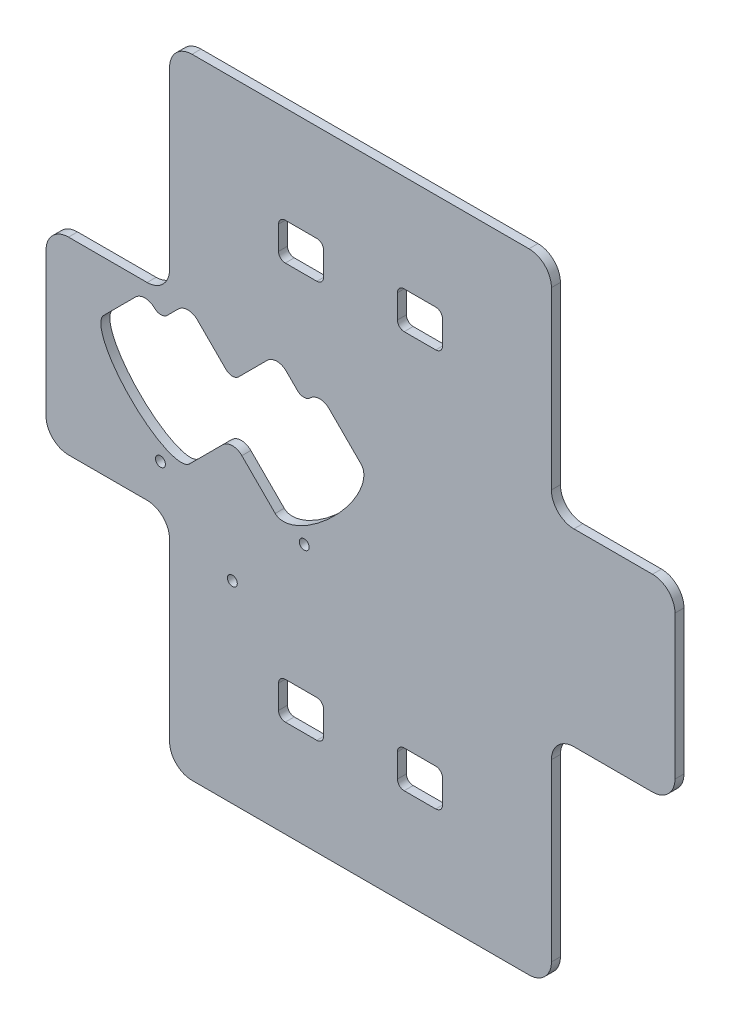
SolidWorks part; units mm, degrees
ref_plane "前视基准面" through (0, 0, 0) normal (0, 0, 1) x (1, 0, 0)
ref_plane "上视基准面" through (0, 0, 0) normal (0, 1, 0) x (1, 0, 0)
ref_plane "右视基准面" through (0, 0, 0) normal (1, 0, 0) x (0, 0, -1)
other "Configuration Table"
sketch "草图1" plane through (0, 0, 0) normal (0, 0, 1) x (1, 0, 0)
  line L24 (85, 52) -> (85, 130)
  line L25 (75, 140) -> (-75, 140)
  line L26 (-85, 130) -> (-85, 52)
  line L27 (-95, 42) -> (-130, 42)
  line L28 (-140, 32) -> (-140, -32)
  line L29 (-130, -42) -> (-95, -42)
  line L30 (-85, -52) -> (-85, -130)
  line L31 (-75, -140) -> (75, -140)
  line L32 (85, -130) -> (85, -52)
  line L33 (95, -42) -> (130, -42)
  line L34 (140, -32) -> (140, 32)
  line L35 (130, 42) -> (95, 42)
  arc A24 (85, 130) -> (75, 140) centre (75, 130) ccw
  arc A25 (-75, 140) -> (-85, 130) centre (-75, 130) ccw
  arc A26 (-95, 42) -> (-85, 52) centre (-95, 52) ccw
  arc A27 (-130, 42) -> (-140, 32) centre (-130, 32) ccw
  arc A28 (-140, -32) -> (-130, -42) centre (-130, -32) ccw
  arc A29 (-85, -52) -> (-95, -42) centre (-95, -52) ccw
  arc A30 (-85, -130) -> (-75, -140) centre (-75, -130) ccw
  arc A31 (75, -140) -> (85, -130) centre (75, -130) ccw
  arc A32 (95, -42) -> (85, -52) centre (95, -52) ccw
  arc A33 (130, -42) -> (140, -32) centre (130, -32) ccw
  arc A34 (140, 32) -> (130, 42) centre (130, 32) ccw
  arc A35 (85, 52) -> (95, 42) centre (95, 52) ccw
extrude "凸台-拉伸1" add sketch "草图1" along normal blind 4
sketch "草图2" plane through (0, 0, 4) normal (0, 0, 1) x (1, 0, 0)
  line L0 (30, -96.75) -> (36.5, -96.75) construction
  line L1 (33.5, -96.75) -> (19.4366, -96.75)
  line L2 (36.5, -93.75) -> (36.5, -83.25)
  line L3 (33.5, -80.25) -> (19.4366, -80.25)
  line L4 (16.4366, -93.75) -> (16.4366, -83.25)
  line L5 (36.5, -96.75) -> (16.4366, -80.25) construction
  line L6 (36.5, -80.25) -> (16.4366, -96.75) construction
  arc A0 (19.4366, -96.75) -> (16.4366, -93.75) centre (19.4366, -93.75) cw
  arc A1 (36.5, -83.25) -> (33.5, -80.25) centre (33.5, -83.25) ccw
  arc A2 (33.5, -96.75) -> (36.5, -93.75) centre (33.5, -93.75) ccw
  arc A3 (19.4366, -80.25) -> (16.4366, -83.25) centre (19.4366, -83.25) ccw
  point P0 (26.4683, -88.5)
  point P5 (25.7917, -88.5)
  point P6 (-3.4862, -67.1345)
  point P7 (25.7917, -88.514)
  point P8 (13.0624, -96.9323)
  point P9 (36.5, -80.25)
  point P11 (16.5604, -94.6714)
  point P12 (36.5, -96.75)
  point P15 (16.5, -80.25)
  dimension "D1" = 3
extrude "切除-拉伸1" cut sketch "草图2" against normal up to next
mirror "镜向1" about plane through (0, 0, 0) normal (1, 0, 0) of "切除-拉伸1" second plane through (0, 0, 0) second plane normal (0, 1, 0)
sketch "草图6" plane through (0, 0, 0) normal (0, 0, -1) x (-1, 0, 0)
  line L0 (57.0634, 102.7787) -> (57.0634, -139.8608) construction
  line L1 (95.9543, 38.0275) -> (88.8832, 30.9565)
  line L2 (-83.8549, -18.541) -> (197.9817, -18.541) construction
  line L3 (152.5228, -18.541) -> (114.339, 19.6427)
  line L4 (57.0634, 76.9184) -> (-38.396, -18.541)
  line L5 (-38.396, -18.541) -> (57.0634, -114.0004)
  line L6 (57.0634, -114.0004) -> (152.5228, -18.541)
  line L7 (152.5228, -18.541) -> (57.0634, 76.9184)
  line L8 (57.0634, 76.9184) -> (30.1933, 50.0483)
  line L9 (30.1933, 50.0483) -> (57.0634, 23.1783)
  line L10 (57.0634, 23.1783) -> (83.9334, 50.0483)
  line L11 (83.9334, 50.0483) -> (57.0634, 76.9184)
  line L12 (57.0634, -114.0004) -> (114.339, -56.7248)
  line L13 (114.339, -56.7248) -> (57.0634, 0.5509)
  line L14 (57.0634, 0.5509) -> (-0.2123, -56.7248)
  line L15 (-0.2123, -56.7248) -> (57.0634, -114.0004)
  line L16 (114.339, 19.6427) -> (76.1553, -18.541)
  line L17 (76.1553, -18.541) -> (114.339, -56.7248)
  line L18 (114.339, -56.7248) -> (152.5228, -18.541)
  line L19 (-38.396, -18.541) -> (-0.2123, -56.7248)
  line L20 (-0.2123, -56.7248) -> (37.9715, -18.541)
  line L21 (37.9715, -18.541) -> (-0.2123, 19.6427)
  line L22 (-0.2123, 19.6427) -> (-38.396, -18.541)
  line L27 (88.8832, 30.9565) -> (76.8624, 42.9773)
  line L28 (18.1725, 38.0275) -> (25.2436, 30.9565)
  line L29 (25.2436, 30.9565) -> (37.2644, 42.9773)
  circle A0 centre (57.0634, -18.541) radius 67.5 construction
  circle A1 centre (57.0634, 50.0483) radius 19 construction
  circle A2 centre (57.0634, -56.7248) radius 40.5 construction
  circle A4 centre (-0.2123, -18.541) radius 27 construction
  ellipse E0 centre (18.8796, 0.5509) end of major axis (-0.2123, 19.6427) minor radius 10
  ellipse E1 centre (95.2472, 0.5509) end of major axis (114.339, 19.6427) minor radius 10
  point P0 (57.0634, -18.541)
  point P4 (57.0634, -18.541)
  point P8 (57.0634, -18.541)
  point P39 (0, 0)
  point P45 (25.0643, 6.7355)
  dimension "D1" = 135
  dimension "D2" = 38
  dimension "D3" = 81
  dimension "D4" = 10
  dimension "D5" = 17
  dimension "D6" = 10
extrude "切除-拉伸2" cut sketch "草图6" against normal up to next contours L13 E1 L7 L1 L27 L10 L9 L29 L28 L4 E0 L14 | L21 E0 | L21 E0 | E1 L16 | E1 L16 region at (-57.0634, 16.6696, 0) region at (-98.2482, -2.4502, 0) region at (-92.2461, 3.5519, 0) region at (-15.8786, -2.4502, 0) region at (-21.8807, 3.5519, 0)
fillet "圆角1" radius 4 3 edges at (-25.2436, 30.9565, 2) (-88.8832, 30.9565, 2) (-57.0634, 23.1783, 2)
fillet "圆角2" radius 6 5 edges at (-57.0634, 0.5509, 2) (-18.1725, 38.0275, 2) (-76.8624, 42.9773, 2) (-37.2644, 42.9773, 2) (-95.9543, 38.0275, 2)
sketch "草图7" plane through (0, 0, 4) normal (0, 0, 1) x (1, 0, 0)
  circle A0 centre (-89.0634, -24.041) radius 2.2
  circle A1 centre (-57.0634, -54.041) radius 2.2
  circle A2 centre (-25.0634, -24.041) radius 2.2
  dimension "D1" = 4.4
  dimension "D2" = 4.4
  dimension "D3" = 4.4
extrude "切除-拉伸3" cut sketch "草图7" against normal up to next
